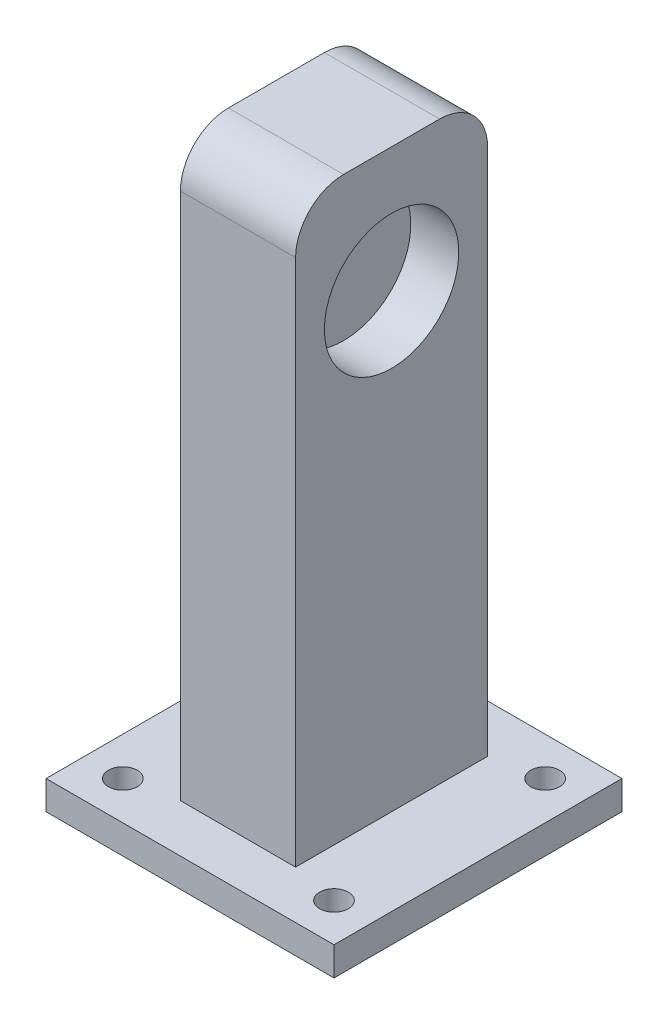
SolidWorks part; units mm, degrees
ref_plane "前视基准面" through (0, 0, 0) normal (0, 0, 1) x (1, 0, 0)
ref_plane "上视基准面" through (0, 0, 0) normal (0, 1, 0) x (1, 0, 0)
ref_plane "右视基准面" through (0, 0, 0) normal (1, 0, 0) x (0, 0, -1)
other "Configuration Table"
sketch "草图4" plane through (0, 0, 0) normal (0, 0, 1) x (1, 0, 0)
  line L0 (0, 0) -> (30, 0)
  line L1 (30, 0) -> (30, 3)
  line L2 (30, 3) -> (0, 3)
  line L3 (0, 3) -> (0, 0)
  dimension "D1" = 30
  dimension "D2" = 3
extrude "凸台-拉伸3" add sketch "草图4" along normal blind 30
sketch "草图5" plane through (0, 0, 0) normal (-1, 0, 0) x (0, 0, 1)
  line L0 (5, 3) -> (25, 3)
  line L1 (30, 3) -> (0, 3) construction
  line L2 (25, 3) -> (25, 63)
  line L3 (25, 63) -> (5, 63)
  line L4 (5, 63) -> (5, 3)
  line L5 (0, 3) -> (0, 0) construction
  dimension "D1" = 60
  dimension "D2" = 20
  dimension "D3" = 5
extrude "凸台-拉伸4" add sketch "草图5" against normal blind 12 from offset 9 offset against normal yes
sketch "草图6" plane through (9, 0, 0) normal (-1, 0, 0) x (0, 0, 1)
  line L0 (5, 3) -> (25, 3) construction
  line L1 (5, 63) -> (5, 3) construction
  circle A0 centre (15, 50) radius 7
  dimension "D1" = 14
  dimension "D2" = 47
  dimension "D3" = 10
extrude "切除-拉伸1" cut sketch "草图6" against normal blind 5 contours A0
extrude "切除-拉伸3" cut sketch "草图6<5>" against normal blind 5 from offset 7 offset against normal yes
sketch "草图6<5>" plane through (9, 0, 0) normal (-1, 0, 0) x (0, 0, 1) same geometry as "草图6"
sketch "草图7" plane through (0, 3, 0) normal (0, 1, 0) x (1, 0, 0)
  line L0 (0, -30) -> (0, 0) construction
  line L1 (30, 0) -> (0, 0) construction
  line L2 (30, -30) -> (30, 0) construction
  line L3 (30, -30) -> (0, -30) construction
  circle A0 centre (4, -4) radius 1.5
  circle A1 centre (26, -4) radius 1.5
  circle A2 centre (26, -26) radius 1.5
  circle A3 centre (4, -26) radius 1.5
  dimension "D1" = 3
  dimension "D10" = 3
  dimension "D11" = 3
  dimension "D12" = 3
  dimension "D2" = 4
  dimension "D3" = 4
  dimension "D4" = 4
  dimension "D5" = 4
  dimension "D6" = 4
  dimension "D7" = 4
  dimension "D8" = 4
  dimension "D9" = 4
extrude "切除-拉伸4" cut sketch "草图7" against normal through all
fillet "圆角1" radius 5 2 edges at (15, 63, 25) (15, 63, 5)
